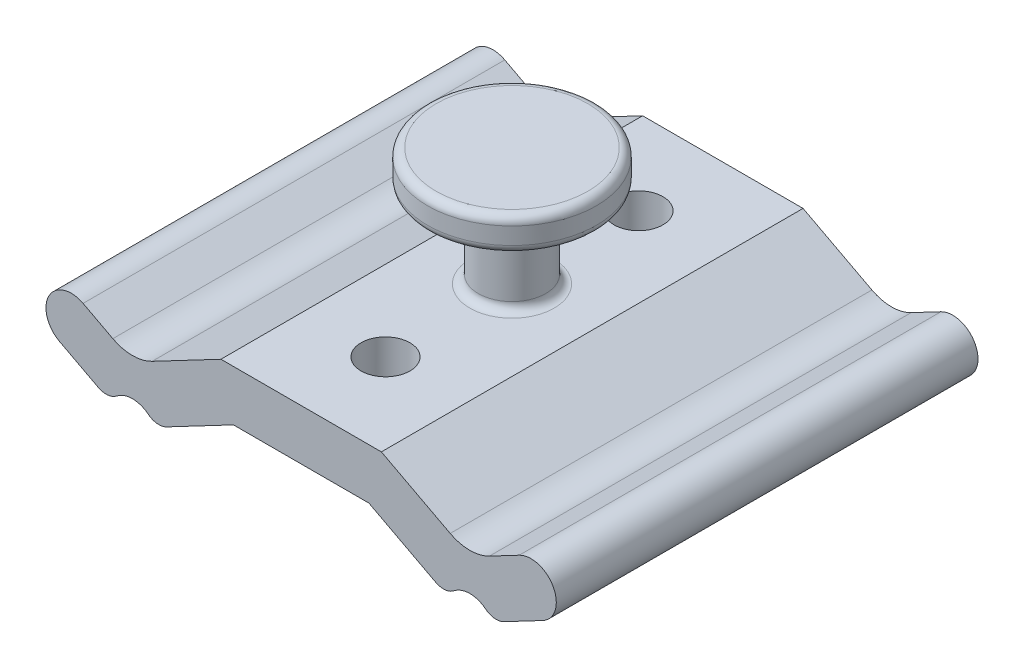
SolidWorks part; units mm, degrees
ref_plane "Front Plane" through (0, 0, 0) normal (0, 0, 1) x (1, 0, 0)
ref_plane "Top Plane" through (0, 0, 0) normal (0, 1, 0) x (1, 0, 0)
ref_plane "Right Plane" through (0, 0, 0) normal (1, 0, 0) x (0, 0, -1)
sketch "Croquis1" plane through (0, 0, 0) normal (0, 0, 1) x (1, 0, 0)
  line L0 (0, 0) -> (8.0292, 0)
  line L1 (8.0292, 0) -> (20, -6.3005)
  line L2 (20, -6.3005) -> (31.3055, -0.3502)
  line L3 (20, 5) -> (20, -6.3005) construction
  circle A1 centre (20, 5) radius 10 construction
  dimension "D1" = 5
  dimension "D3" = 20
  dimension "D2" = 124.482
  dimension "D4" = 20
extrude "Extruir-Lámina1" add sketch "Croquis1" against normal blind 25 and the other way blind 25 thin thin type one direction reverse wall 6
fillet "Redondeo1" radius 5 1 edges at (20, 0.4798, 0)
sketch "Croquis2" plane through (0, 0, 0) normal (0, 0, 1) x (1, 0, 0)
  circle A0 centre (20, -6.3005) radius 3
  dimension "D1" = 6
extrude "Cortar-Extruir1" cut sketch "Croquis2" against normal through all both and the other way through all
fillet "Redondeo2" 2 edges at (31.3055, -0.3502, 0) (28.5109, 4.9593, 0) type full round first side face at (26.9801, -2.6267, 0) second side face at (25.4199, 3.3324, 0) middle face at (29.9082, 2.3046, 0)
fillet "Redondeo3" radius 2 2 edges at (22.6547, -4.9033, 0) (17.3453, -4.9033, 0)
mirror "Simetría1" about plane through (0, 0, 0) normal (1, 0, 0) of "Redondeo3", "Redondeo2", "Redondeo1", "Cortar-Extruir1", "Extruir-Lámina1"
hole_wizard "Taladro de margen para M51" positions "Croquis3" profile "Croquis4" hole size "M5" standard "DIN" end condition through all
sketch "Croquis3" plane through (0, 6, 0) normal (0, 1, 0) x (1, 0, 0)
  line L0 (0, 15) -> (0, -15)
  point P1 (0, 15)
  point P2 (0, -15)
  dimension "D1" = 30
sketch "Croquis4" plane through (0, 6, -15) normal (1, 0, 0) x (0, 0, 1)
  line L0 (0, 0) -> (0, 10.3963)
  line L1 (0, 10.3963) -> (2.9, 10.3963)
  line L2 (2.9, 10.3963) -> (2.9, 0)
  line L5 (2.9, 0) -> (0, 0)
  line L11 (0, -6.35) -> (0, 107.95) construction
  dimension "Diámetro de taladro hasta el siguiente" = 5.8
  dimension "Profundidad de taladro hasta el siguiente" = 10.3963
sketch "Croquis5" plane through (0, 0, 0) normal (0, 0, 1) x (1, 0, 0)
  line L0 (0, 0) -> (0, 20)
  line L1 (0, 20) -> (10, 20)
  line L2 (10, 20) -> (10, 16)
  line L3 (10, 16) -> (4, 16)
  line L4 (4, 16) -> (4, 0)
  line L5 (-8.0292, 0) -> (8.0292, 0) construction
  line L6 (4, 0) -> (0, 0)
  dimension "D1" = 20
  dimension "D2" = 4
  dimension "D3" = 10
  dimension "D4" = 4
revolve "Revolución1" add sketch "Croquis5" angle 360 about L0
fillet "Redondeo4" radius 1 4 edges at (0, 16, -10) (0, 20, -10) (0, 16, -4) (-4, 6, 0)
